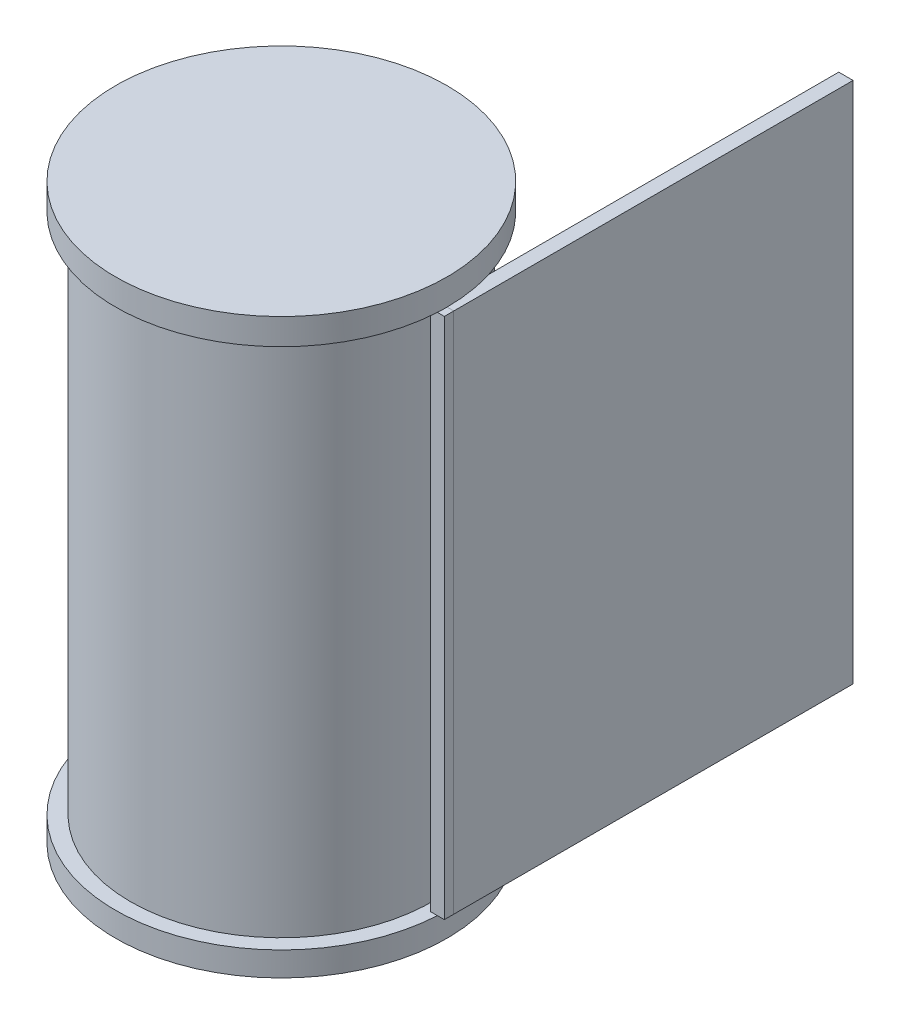
SolidWorks part; units mm, degrees
ref_plane "Alzado" through (0, 0, 0) normal (0, 0, 1) x (1, 0, 0)
ref_plane "Planta" through (0, 0, 0) normal (0, 1, 0) x (1, 0, 0)
ref_plane "Vista lateral" through (0, 0, 0) normal (1, 0, 0) x (0, 0, -1)
sketch "Croquis1" plane through (0, 0, 0) normal (0, 0, 1) x (1, 0, 0)
  line L0 (-92.5908, 0) -> (91.6632, 0) construction
  line L1 (91.6632, 0) -> (0, 0) construction
  line L2 (0, 0) -> (0, -77.4814) construction
  line L3 (0, -77.4814) -> (0, 71.3544) construction
  line L4 (0, 46.9938) -> (0, -69.4093)
  line L5 (0, -69.4093) -> (35.2914, -69.4093)
  line L6 (35.2914, -69.4093) -> (35.2914, -64.2447)
  line L7 (35.2914, -64.2447) -> (32.1132, -64.2447)
  line L8 (32.1132, -64.2447) -> (32.1132, 46.9938)
  line L9 (32.1132, 46.9938) -> (35.2914, 46.9938)
  line L10 (35.2914, 46.9938) -> (35.2914, 52.5558)
  line L11 (35.2914, 52.5558) -> (0, 52.5558)
  line L12 (0, 52.5558) -> (0, -69.4093)
  dimension "D1" = 184.254
  dimension "D2" = 91.6632
  dimension "D3" = 77.4814
  dimension "D4" = 148.8359
  dimension "D5" = 116.4032
  dimension "D6" = 35.2914
  dimension "D7" = 5.1646
  dimension "D8" = 3.1782
  dimension "D9" = 111.2385
  dimension "D10" = 3.1782
  dimension "D11" = 5.5619
  dimension "D12" = 35.2914
  dimension "D13" = 121.9651
revolve "Revolución1" add sketch "Croquis1" angle 360 about L3 region at (16.2089, -8.409, 0)
shell "Vaciado1" thickness 10 removed face at (0, -69.4093, -35.2914)
ref_plane "Plano1" through (0, 0, 0) normal (0, 0, 1) x (1, 0, 0)
sketch "Croquis3" plane through (35.2118, 0, 0) normal (0, 0, 1) x (1, 0, 0)
  line L0 (0, 61.5287) -> (0, -89.4436) construction
  line L1 (-1.5, 46.9938) -> (-1.5, -64.2447)
  line L2 (1.5, 46.9938) -> (1.5, -64.2447)
  line L5 (1.5, -64.2447) -> (-1.5, -64.2447)
  line L6 (-1.5, 46.9938) -> (1.5, 46.9938)
  dimension "D1" = 150.9723
  dimension "D2" = 3
extrude "Saliente-Extruir1" add sketch "Croquis3" against normal blind 85 draft 0.018 and the other way blind 2 draft outward yes
